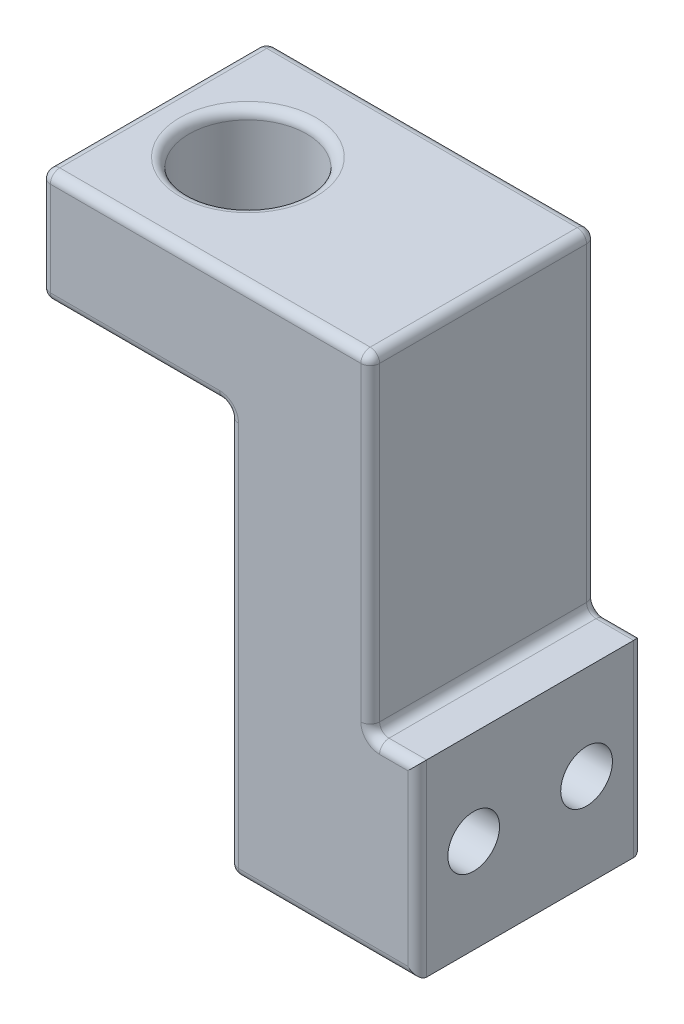
SolidWorks part; units mm, degrees
material "PLA"
ref_plane "Alzado" through (0, 0, 0) normal (0, 0, 1) x (1, 0, 0)
ref_plane "Planta" through (0, 0, 0) normal (0, 1, 0) x (1, 0, 0)
ref_plane "Vista lateral" through (0, 0, 0) normal (1, 0, 0) x (0, 0, -1)
sketch "Sketch4" plane through (0, 0, 0) normal (0, 1, 0) x (1, 0, 0)
  line L1 (0, 0) -> (40, 0)
  line L2 (0, 0) -> (0, 24)
  line L3 (0, 24) -> (40, 24)
  line L4 (40, 0) -> (40, 24)
  dimension "D1" = 24
  dimension "D2" = 40
extrude "Boss-Extrude2" add sketch "Sketch4" along normal blind 55
sketch "Sketch6" plane through (0, 0, 0) normal (0, 0, 1) x (1, 0, 0)
  line L0 (0, 55) -> (35, 55)
  line L1 (0, 55) -> (40, 55) construction
  line L2 (35, 55) -> (35, 20)
  line L3 (35, 20) -> (40, 20)
  line L4 (40, 55) -> (40, 0) construction
  line L5 (40, 20) -> (40, 0)
  line L6 (40, 0) -> (20, 0)
  line L7 (0, 0) -> (40, 0) construction
  line L8 (20, 0) -> (20, 43)
  line L9 (20, 43) -> (0, 43)
  line L10 (0, 55) -> (0, 0) construction
  line L11 (0, 43) -> (0, 55)
  line L12 (35, 55) -> (40, 55)
  line L13 (40, 55) -> (40, 20)
  line L14 (0, 43) -> (0, 0)
  line L15 (0, 0) -> (20, 0)
  line M9 (0, 0) -> (40, 0)
  line M10 (40, 0) -> (40, 55)
  line M11 (40, 55) -> (0, 55)
  line M12 (0, 55) -> (0, 0)
  dimension "D1" = 5
  dimension "D2" = 20
  dimension "D3" = 20
  dimension "D4" = 12
extrude "Cut-Extrude1" cut sketch "Sketch6" against normal through all contours L2 L3 M10 M11 | L8 L9 M12 M9 region at (37.5, 37.5, 0) region at (10, 21.5, 0)
sketch "Sketch7" plane through (0, 43, 0) normal (0, -1, 0) x (-1, 0, 0)
  line L0 (-10, 0) -> (-10, 24) construction
  line L1 (-20, 0) -> (0, 0) construction
  line L2 (-20, 24) -> (0, 24) construction
  circle A0 centre (-10, 12) radius 6.25
  dimension "D1" = 12.5
extrude "Cut-Extrude2" cut sketch "Sketch7" against normal through all
sketch "Sketch8" plane through (20, 0, 0) normal (-1, 0, 0) x (0, 0, 1)
  line L0 (0, 10) -> (-24, 10) construction
  line L1 (0, 0) -> (0, 43) construction
  line L2 (-24, 0) -> (-24, 43) construction
  line L3 (-24, 0) -> (0, 0) construction
  circle A0 centre (-10, 10) radius 2.5
  circle A1 centre (-14, 10) radius 2.5
  dimension "D2" = 10
  dimension "D4" = 5
  dimension "D5" = 5
  dimension "D1" = 10
  dimension "D3" = 10
sketch "Sketch10" plane through (20, 0, 0) normal (-1, 0, 0) x (0, 0, 1)
  line L0 (-24, 10) -> (0, 10) construction
  line L1 (-24, 0) -> (-24, 43) construction
  line L2 (0, 0) -> (0, 43) construction
  line L3 (-24, 0) -> (0, 0) construction
  circle A0 centre (-18, 10) radius 2.75
  circle A1 centre (-6, 10) radius 2.75
  dimension "D1" = 5.5
  dimension "D2" = 5.5
  dimension "10" = 10
  dimension "D3" = 6
  dimension "D4" = 6
extrude "Cut-Extrude4" cut sketch "Sketch10" against normal through all
sketch "Sketch12" plane through (20, 0, 0) normal (-1, 0, 0) x (0, 0, 1)
  line L0 (-24, 10) -> (0, 10) construction
  line L1 (-24, 0) -> (-24, 43) construction
  line L2 (0, 0) -> (0, 43) construction
  line L3 (-24, 0) -> (0, 0) construction
  circle A0 centre (-18, 10) radius 4.5
  circle A1 centre (-6, 10) radius 4.5
  dimension "D1" = 9
  dimension "D2" = 9
  dimension "10" = 10
extrude "Cut-Extrude5" cut sketch "Sketch12" against normal blind 8
fillet "Fillet1" radius 1 25 edges at (35, 20, -12) (10, 43, -24) (30, 0, -24) (40, 10, -24) (37.5, 20, -24) (35, 37.5, -24) (40, 10, 0) (30, 0, 0) (10, 43, 0) (35, 37.5, 0) (37.5, 20, 0) (17.5, 55, -24) (35, 55, -12) (17.5, 55, 0) (10, 55, -18.25) (0, 55, -12) (0, 49, 0) (0, 43, -12) (0, 49, -24) (20, 0, -12) (20, 21.5, -24) (20, 43, -12) (20, 21.5, 0) (20, 10, -1.5) (20, 10, -13.5)
fillet "Fillet2" radius 1 1 edges at (10, 43, -18.25)
